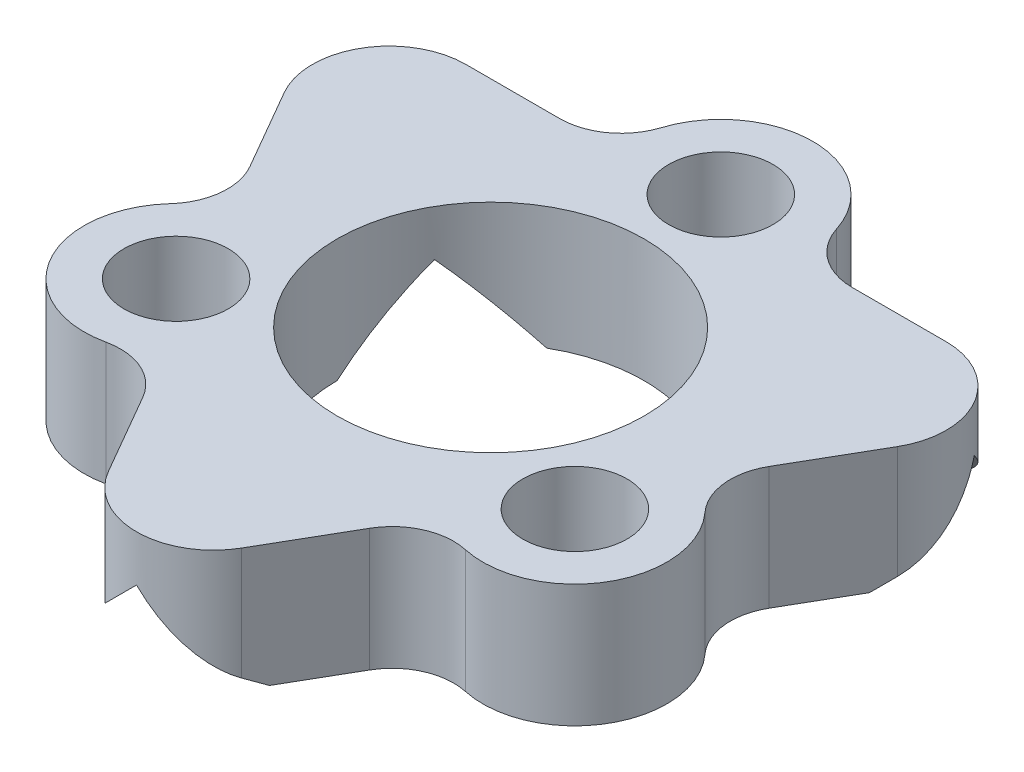
SolidWorks part; units mm, degrees
note: '?' marks a value the reader was unsure of.
material "Chrome Stainless Steel"
ref_plane "Front Plane" through (0, 0, 0) normal (0, 0, 1) x (1, 0, 0)
ref_plane "Top Plane" through (0, 0, 0) normal (0, 1, 0) x (1, 0, 0)
ref_plane "Right Plane" through (0, 0, 0) normal (1, 0, 0) x (0, 0, -1)
sketch "Sketch1" plane through (0, 0, 0) normal (0, 1, 0) x (1, 0, 0)
  line L0 (-3.8909, 3.147) -> (-2.3605, 0.4962)
  line L1 (8.2641, -10.4061) -> (9.7945, -7.7554)
  line L2 (13.9239, 6.897) -> (10.8631, 6.897)
  line L3 (-0.528, -3.9469) -> (15.4056, 5.2524) construction
  line L4 (6.099, 6.897) -> (6.099, -11.9869) construction
  line L5 (10.4292, -2.6207) -> (-3.7639, 5.5736) construction
  line L6 (2.4036, -7.7554) -> (3.934, -10.4061)
  line L7 (-6.056, 6.897) -> (3.1381, 6.897) construction
  line L8 (18.254, 6.897) -> (6.099, -14.1561) construction
  line L9 (6.099, -14.1561) -> (-6.056, 6.897) construction
  line L10 (-6.056, 6.897) -> (18.254, 6.897) construction
  line L11 (14.5586, 0.4962) -> (16.089, 3.147)
  line L12 (1.335, 6.897) -> (-1.7258, 6.897)
  line L13 (9.06, 6.897) -> (18.254, 6.897) construction
  circle A0 centre (6.099, -0.1207) radius 5
  circle A1 centre (6.099, -0.1207) radius 7.5 construction
  arc A2 (0.2445, -6.8015) -> (-2.614, -1.8505) centre (-0.3961, -3.8707) cw
  arc A3 (2.4036, -7.7554) -> (0.2445, -6.8015) centre (0.6715, -8.7554) ccw
  arc A4 (-3.8909, 3.147) -> (-1.7258, 6.897) centre (-1.7258, 4.397) cw
  arc A5 (8.2641, -10.4061) -> (3.934, -10.4061) centre (6.099, -9.1561) cw
  arc A6 (13.9239, 6.897) -> (16.089, 3.147) centre (13.9239, 4.397) cw
  arc A7 (-2.3605, 0.4962) -> (-2.614, -1.8505) centre (-4.0926, -0.5038) cw
  arc A8 (9.7945, -7.7554) -> (11.9536, -6.8015) centre (11.5265, -8.7554) cw
  arc A9 (14.8121, -1.8505) -> (11.9536, -6.8015) centre (12.5942, -3.8707) cw
  arc A10 (14.8121, -1.8505) -> (14.5586, 0.4962) centre (16.2906, -0.5038) cw
  arc A11 (3.2406, 8.2899) -> (8.9575, 8.2899) centre (6.099, 7.3793) cw
  arc A12 (1.335, 6.897) -> (3.2406, 8.2899) centre (1.335, 8.897) ccw
  arc A13 (10.8631, 6.897) -> (8.9575, 8.2899) centre (10.8631, 8.897) cw
  point P7 (-0.3961, -3.8707)
  point P8 (6.099, 7.3793)
  point P9 (-6.056, 6.897)
  point P10 (12.5942, -3.8707)
  point P12 (6.099, -14.1561)
  point P16 (6.099, -0.1207)
  point P30 (1.502, -6.1939)
  dimension "D1" = 10
  dimension "D5" = 15
  dimension "D6" = 2.5
  dimension "D7" = 3
  dimension "D8" = 2
  dimension "D9" = 2
  dimension "D10" = 3
  dimension "D11" = 2
  dimension "D12" = 3
  dimension "D2" = 120
  dimension "D3" = 240
  dimension "D4" = 24.31
extrude "Extrude1" add sketch "Sketch1" along normal blind 4
hole_wizard "M3 Clearance Hole1" positions "3DSketch1" profile "Sketch6" hole size "M3" standard "Ansi Metric"
sketch3d "3DSketch1"
  line L0 (-0.3961, 4, 3.8707) -> (-0.3961, 0, 3.8707) construction
  point P0 (-0.3961, 4, 3.8707)
sketch "Sketch6" plane through (-0.3961, 4, 3.8707) normal (1, 0, 0) x (0, 0, 1)
  line L0 (0, 0) -> (0, 11.0215)
  line L1 (0, 11.0215) -> (1.7, 10)
  line L2 (1.7, 10) -> (1.7, 0)
  line L5 (1.7, 0) -> (0, 0)
  line L10 (0, 11.0215) -> (-1.7, 10) construction
  line L11 (0, -6.35) -> (0, 107.95) construction
  dimension "Hole Dia." = 3.4
  dimension "Hole Depth" = 10
  dimension "Drill Angle" = 118
pattern_circular "CirPattern2" count 3 over 360 about axis through (6.099, 0, 0.1207) along (0, 1, 0) of "M3 Clearance Hole1"
sketch "GrooveSketch" plane through (0, 0, 0) normal (0, 0, 1) x (1, 0, 0)
  line L0 (3.934, 4) -> (8.2641, 0) construction
  line L1 (8.2641, 4) -> (3.934, 0) construction
  line L2 (6.099, 0) -> (6.099, 2.5) construction
  line L3 (3.934, 0) -> (8.2641, 0) construction
  line L4 (6.099, 0) -> (0.2445, 0) construction
  line L5 (6.099, 0) -> (11.9536, 0) construction
  line L6 (6.099, 2.5) -> (3.599, 0)
  line L7 (6.099, 2.5) -> (8.599, 0)
  circle A0 centre (6.099, -0.8658) radius 2.38 construction
  dimension "D2" = 4.76
  dimension "D1" = 2.5
  dimension "D3" = 90
  dimension "D4" = 45
extrude "Extrude4" cut sketch "GrooveSketch" along normal up to next from surface
ref_axis "Axis1" through (6.099, 4, 0.1207) along (0, -1, 0)?
ref_plane "Plane1" through (4.6266, 0, 2.6711) normal (-0.866, 0, -0.5) x (-0.5, 0, 0.866)
ref_plane "Plane2" through (4.522, 0, -2.6108) normal (0.866, 0, -0.5) x (-0.5, 0, -0.866)
sketch "Sketch9" plane through (4.6266, 0, 2.6711) normal (-0.866, 0, -0.5) x (-0.5, 0, 0.866)
  line L2 (-2.945, 0) -> (-2.945, 2.5) construction
  line L3 (-2.945, 0) -> (-8.7995, 0) construction
  line L4 (-2.945, 0) -> (2.9096, 0) construction
  line L5 (-2.945, 2.5) -> (-5.445, 0)
  line L6 (-2.945, 2.5) -> (-0.445, 0)
  line L7 (-2.945, 4) -> (-2.945, 0) construction
  line L8 (-5.11, 0) -> (-0.7799, 0) construction
  circle A0 centre (-2.945, -0.8658) radius 2.38 construction
  dimension "D1" = 4.76
  dimension "D2" = 2.5
  dimension "D3" = 90
  dimension "D4" = 45
extrude "Extrude5" cut sketch "Sketch9" along normal through all from surface
sketch "Sketch10" plane through (4.522, 0, -2.6108) normal (0.866, 0, -0.5) x (-0.5, 0, -0.866)
  line L2 (-3.1541, 0) -> (-3.1541, 2.5) construction
  line L3 (-3.1541, 0) -> (13.4676, 0) construction
  line L4 (-3.1541, 0) -> (25.1768, 0) construction
  line L5 (-3.1541, 2.5) -> (-5.6541, 0)
  line L6 (-3.1541, 2.5) -> (-0.6541, 0)
  line L7 (-5.3191, 0) -> (-0.989, 0) construction
  line L8 (-3.1541, 4) -> (-3.1541, 0) construction
  circle A0 centre (-3.1541, -0.8658) radius 2.38 construction
  dimension "D1" = 4.76
  dimension "D2" = 2.5
  dimension "D3" = 90
  dimension "D4" = 45
extrude "Extrude6" cut sketch "Sketch10" along normal through all from surface
